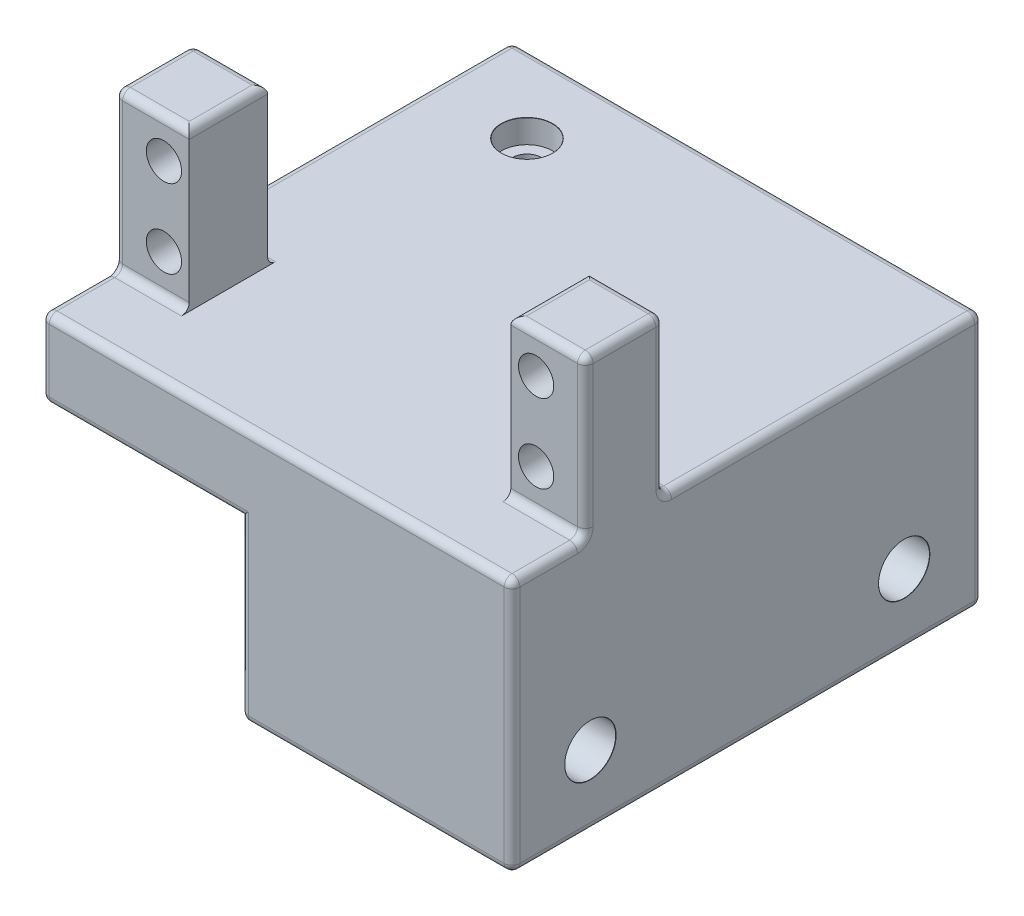
SolidWorks part; units mm, degrees
note: The reader was unsure of these and kept them because the rebuilt part matched: shared geometry of "Sketch1<3>", "Sketch1<4>".
ref_plane "Front Plane" through (0, 0, 0) normal (0, 0, 1) x (1, 0, 0)
ref_plane "Top Plane" through (0, 0, 0) normal (0, 1, 0) x (1, 0, 0)
ref_plane "Right Plane" through (0, 0, 0) normal (1, 0, 0) x (0, 0, -1)
sketch "Sketch1" plane through (0, 0, 0) normal (0, 1, 0) x (1, 0, 0)
  line L0 (-30, 30) -> (-30, -30)
  line L8 (-30, -10.65) -> (-20.5, -10.65)
  line L9 (-20.5, -10.65) -> (-20.5, -20.65)
  line L10 (-20.5, -20.65) -> (-30, -20.65)
  line L11 (20.5, -20.65) -> (30, -20.65)
  line L12 (0, -699.3249) -> (0, 34266.9223) construction
  line L13 (-699.3249, 0) -> (34266.9223, 0) construction
  line L17 (20.5, -10.65) -> (20.5, -20.65)
  line L18 (30, -10.65) -> (20.5, -10.65)
  line L19 (30, 30) -> (30, -30)
  line L20 (-30, 30) -> (30, 30)
  line L22 (30, -30) -> (-30, -30)
  line L23 (-4.6, 30) -> (-4.6, -30)
  point P0 (0, 0)
  point P18 (0, 0)
  point P19 (-30, 0)
  dimension "D1" = 60
  dimension "D2" = 41
  dimension "D3" = 25.4
  dimension "D4" = 10
  dimension "D5" = 9.35
  dimension "D6" = 60
extrude "Boss-Extrude1" add sketch "Sketch1" against normal blind 10
extrude "Boss-Extrude2" add sketch "Sketch1<3>" along normal blind 20 contours L10 L9 L8 L0 | L19 L18 L17 L11
sketch "Sketch1<3>" plane through (0, 0, 0) normal (0, 1, 0) x (1, 0, 0) same geometry as "Sketch1"
extrude "Boss-Extrude3" add sketch "Sketch1<4>" against normal blind 22.5 from surface at -10 starting at face at (0, -10, 0)
sketch "Sketch1<4>" plane through (0, 0, 0) normal (0, 1, 0) x (1, 0, 0) same geometry as "Sketch1"
sketch "Sketch2" plane through (30, 0, 0) normal (1, 0, 0) x (0, 0, -1)
  line L0 (-20, -23.49) -> (20, -23.49) construction
  point P0 (-20, -23.49)
  point P1 (20, -23.49)
  point P4 (0, -23.49)
  dimension "D1" = 40
  dimension "D2" = 13.49
hole_wizard "CBORE for M3 SHCS1" positions "Sketch2" profile "Sketch3" counterbore size "M3" standard "ANSI Metric"
sketch "Sketch3" plane through (30, -23.49, 20) normal (0, 1, 0) x (0, 0, -1)
  line L0 (0, 0) -> (0, 35.6815)
  line L1 (0, 35.6815) -> (1.8, 34.6)
  line L2 (1.8, 34.6) -> (1.8, 23)
  line L3 (1.8, 23) -> (3.25, 23)
  line L5 (3.25, 23) -> (3.25, 0.025)
  line L6 (3.25, 0.025) -> (3.275, 0)
  line L7 (3.275, 0) -> (0, 0)
  line L8 (-3.25, 0.025) -> (-3.275, 0) construction
  line L10 (0, 35.6815) -> (-1.8, 34.6) construction
  line L11 (0, -6.35) -> (0, 107.95) construction
  dimension "Hole Dia." = 3.6
  dimension "Hole Depth" = 34.6
  dimension "C'Bore Dia." = 6.5
  dimension "C'Bore Depth" = 23
  dimension "Near C'Sink Dia." = 6.55
  dimension "Near C'Sink Angle" = 90
  dimension "Drill Angle" = 118
sketch "Sketch4" plane through (0, 0, 0) normal (0, 1, 0) x (1, 0, 0)
  point P0 (-18.09, 20)
  point P1 (0, 0)
  point P3 (-12.2404, 20)
  dimension "D1" = 11.91
hole_wizard "CBORE for M3 SHCS2" positions "Sketch4" profile "Sketch5" counterbore size "M3" standard "ANSI Metric"
sketch "Sketch5" plane through (-18.09, 0, -20) normal (1, 0, 0) x (0, 0, 1)
  line L0 (0, 0) -> (0, 11.0815)
  line L1 (0, 11.0815) -> (1.8, 10)
  line L2 (1.8, 10) -> (1.8, 3)
  line L3 (1.8, 3) -> (3.25, 3)
  line L5 (3.25, 3) -> (3.25, 0.025)
  line L6 (3.25, 0.025) -> (3.275, 0)
  line L7 (3.275, 0) -> (0, 0)
  line L8 (-3.25, 0.025) -> (-3.275, 0) construction
  line L10 (0, 11.0815) -> (-1.8, 10) construction
  line L11 (0, -6.35) -> (0, 107.95) construction
  dimension "Hole Dia." = 3.6
  dimension "Hole Depth" = 10
  dimension "C'Bore Dia." = 6.5
  dimension "C'Bore Depth" = 3
  dimension "Near C'Sink Dia." = 6.55
  dimension "Near C'Sink Angle" = 90
  dimension "Drill Angle" = 118
sketch "Sketch6" plane through (0, 0, 20.65) normal (0, 0, 1) x (1, 0, 0)
  line L0 (0, -1000) -> (0, 49000) construction
  circle A0 centre (-23.725, 15) radius 2.25
  circle A1 centre (-23.725, 5) radius 2.25
  circle A2 centre (-23.725, 15) radius 2.15 construction
  circle A3 centre (23.725, 5) radius 2.25
  circle A4 centre (23.725, 15) radius 2.25
  point P9 (-22.446, 5.0821)
  point P10 (0, 0)
  dimension "D2" = 4.5
  dimension "D1" = 10
extrude "Cut-Extrude1" cut sketch "Sketch6" against normal up to surface (10 mm away) up to face at (-25.25, 10, 10.65)
fillet "Fillet1" radius 1 35 edges at (-4.6, -32.5, 0) (12.7, -32.5, 30) (-4.6, -21.25, 30) (-17.3, -10, 30) (0, 0, 30) (30, -32.5, 0) (30, -16.25, 30) (30, 0, 25.325) (30, 10, 20.65) (30, 10, 10.65) (30, 0, -9.675) (25.25, 20, 20.65) (20.5, 20, 15.65) (25.25, 20, 10.65) (30, 20, 15.65) (-25.25, 20, 10.65) (-20.5, 20, 15.65) (-25.25, 20, 20.65) (-17.3, -10, -30) (-4.6, -21.25, -30) (12.7, -32.5, -30) (30, -16.25, -30) (0, 0, -30) (-30, 10, 10.65) (-30, 20, 15.65) (-30, 10, 20.65) (-30, 0, 25.325) (-30, -5, 30) (-30, -10, 0) (-30, -5, -30) (-30, 0, -9.675) (-25.25, 0, 10.65) (25.25, 0, 10.65) (-25.25, 0, 20.65) (25.25, 0, 20.65)
